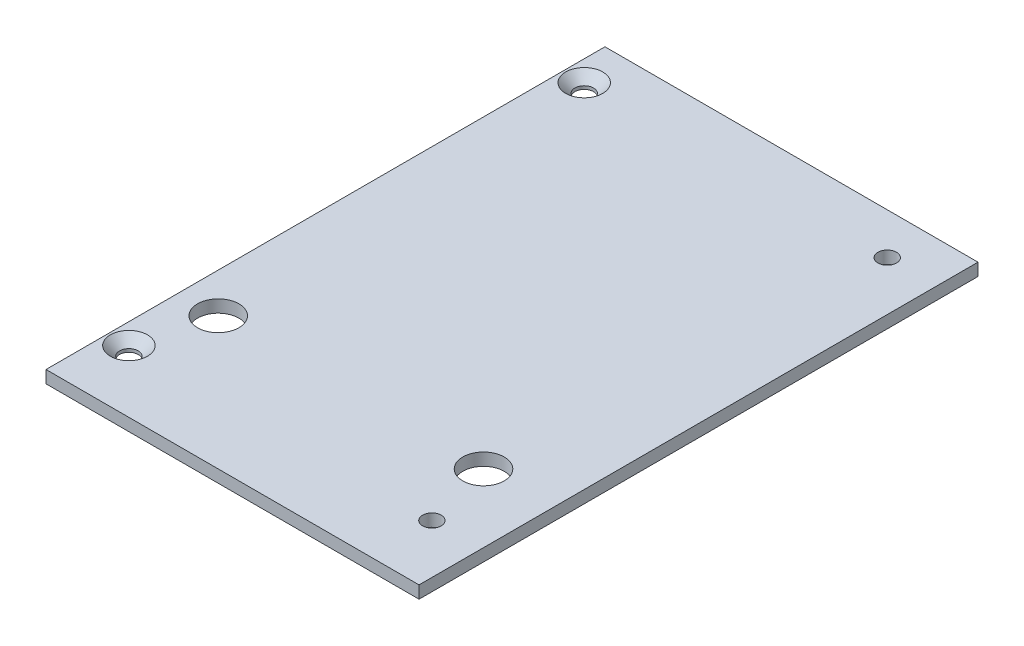
SolidWorks part; units mm, degrees
ref_plane "Alzado" through (0, 0, 0) normal (0, 0, 1) x (1, 0, 0)
ref_plane "Planta" through (0, 0, 0) normal (0, 1, 0) x (1, 0, 0)
ref_plane "Vista lateral" through (0, 0, 0) normal (1, 0, 0) x (0, 0, -1)
sketch "Sketch1" plane through (0, 0, 0) normal (0, 1, 0) x (1, 0, 0)
  line L1 (-45, -67.425) -> (45, -67.425)
  line L2 (-45, -67.425) -> (-45, 67.425)
  line L3 (-45, 67.425) -> (45, 67.425)
  line L4 (45, -67.425) -> (45, 67.425)
  line L5 (-45, -67.425) -> (45, 67.425) construction
  line L6 (-45, 67.425) -> (45, -67.425) construction
  circle A0 centre (-40, 57.425) radius 2.25
  circle A1 centre (33.1, 57.425) radius 2.25
  circle A2 centre (33.1, -52.425) radius 2.25
  circle A3 centre (-40, -52.425) radius 2.25
  point P0 (0, 0)
  dimension "D1" = 134.85
  dimension "D2" = 90
extrude "Boss-Extrude1" add sketch "Sketch1" along normal blind 3
sketch "Sketch2" plane through (0, 0, 0) normal (0, -1, 0) x (1, 0, 0)
  circle A0 centre (-35.45, 35.425) radius 5
  circle A1 centre (28.55, 35.425) radius 5
  dimension "D1" = 10
extrude "Cut-Extrude1" cut sketch "Sketch2" against normal blind 10
sketch "Sketch3" plane through (0, 0, 0) normal (0, -1, 0) x (1, 0, 0)
  line L0 (-35, -67.425) -> (28.1, -67.425) construction
  line L1 (45, -67.425) -> (-45, -67.425) construction
  line L2 (-35, -72.8739) -> (-35, -0.3806) construction
  line L3 (28.1, -0.3806) -> (28.1, -72.8739) construction
  line L4 (28.1, -67.425) -> (28.1, -0.3806) construction
  line L5 (27.3285, 2.2876) -> (0.7785, 44.3637) construction
  line L6 (-34.2285, 2.2876) -> (-7.6785, 44.3637) construction
  line L7 (-7.6785, 44.3637) -> (-34.2285, 2.2876) construction
  line L8 (-35, -0.3806) -> (-35, -67.425) construction
  line L9 (-34.6, -0.3806) -> (-34.6, -67.025)
  line L10 (-34.6, -67.025) -> (27.7, -67.025)
  line L11 (27.7, -67.025) -> (27.7, -0.3806)
  line L12 (26.9903, 2.0741) -> (0.4403, 44.1502)
  line L13 (-7.3403, 44.1502) -> (-33.8903, 2.0741)
  line L14 (-29.6, -0.4963) -> (-29.6, -62.025)
  line L15 (-29.6, -62.025) -> (22.7, -62.025)
  line L16 (22.7, -62.025) -> (22.7, -0.4963)
  line L17 (22.7, -0.4963) -> (-3.45, 40.9459)
  line L18 (-3.45, 40.9459) -> (-29.6, -0.4963)
  arc A0 (28.1, -0.3806) -> (27.3285, 2.2876) centre (23.1, -0.3806) ccw construction
  arc A1 (28.1, -0.3806) -> (27.3285, 2.2876) centre (23.1, -0.3806) ccw construction
  arc A2 (0.7785, 44.3637) -> (-7.6785, 44.3637) centre (-3.45, 41.6954) ccw construction
  arc A3 (-34.2285, 2.2876) -> (-35, -0.3806) centre (-30, -0.3806) ccw construction
  arc A4 (-34.2285, 2.2876) -> (-35, -0.3806) centre (-30, -0.3806) ccw construction
  arc A5 (27.7, -0.3806) -> (26.9903, 2.0741) centre (23.1, -0.3806) ccw
  arc A6 (0.4403, 44.1502) -> (-7.3403, 44.1502) centre (-3.45, 41.6954) ccw
  arc A7 (-33.8903, 2.0741) -> (-34.6, -0.3806) centre (-30, -0.3806) ccw
  arc A8 (22.7, -0.4963) -> (22.7, -0.4963) centre (22.7, -0.4963) ccw
  arc A9 (-3.45, 40.9459) -> (-3.45, 40.9459) centre (-3.45, 40.9459) ccw
  arc A10 (-29.6, -0.4963) -> (-29.6, -0.4963) centre (-29.6, -0.4963) ccw
  dimension "D1" = 0.4
  dimension "D2" = 5
extrude "Boss-Extrude2" add sketch "Sketch3" along normal blind 3
fillet "Fillet1" radius 10 5 edges at (9.625, 0, 20.2248) (22.7, 0, -31.2606) (-3.45, 0, -62.025) (-29.6, 0, -31.2606) (-16.525, 0, 20.2248)
sketch "Sketch4" plane through (0, 3, 0) normal (0, 1, 0) x (1, 0, 0)
  line L0 (-40, 57.425) -> (33.1, 57.425) construction
  line L1 (-40, -52.425) -> (33.1, -52.425) construction
  line L3 (-45, 67.425) -> (-45, -67.425) construction
  line L4 (28.1, 0.3806) -> (28.1, 72.8739) construction
  line L5 (-45, -67.425) -> (45, -67.425) construction
  line L6 (45, 67.425) -> (-45, 67.425) construction
  dimension "D1" = 5
  dimension "D2" = 5
  dimension "D3" = 15
  dimension "D4" = 10
hole_wizard "Avellanado para tornillo tapón avellanado de clavija hexagonal de M41" positions "Croquis3D1" profile "Croquis1" countersink size "M4" standard "ISO"
sketch3d "Croquis3D1"
  line L0 (-40, 3, 52.425) -> (-40, 0, 52.425) construction
  line L1 (-40, 3, -57.425) -> (-40, 0, -57.425) construction
  point P0 (-40, 3, 52.425)
  point P5 (-40, 3, -57.425)
sketch "Croquis1" plane through (-40, 3, 52.425) normal (1, 0, 0) x (0, 0, 1)
  line L0 (0, 0) -> (0, 7.3519)
  line L1 (0, 7.3519) -> (2.25, 6)
  line L2 (2.25, 6) -> (2.25, 2.23)
  line L3 (2.25, 2.23) -> (4.48, 0)
  line L5 (4.48, 0) -> (0, 0)
  line L6 (-2.25, 2.23) -> (-4.48, 0) construction
  line L10 (0, 7.3519) -> (-2.25, 6) construction
  line L11 (0, -6.35) -> (0, 107.95) construction
  dimension "Diámetro de taladro" = 4.5
  dimension "Profundidad de taladro" = 6
  dimension "Ángulo de avellanado cercano" = 8.96
  dimension "Ángulo de avellanado lejano" = 90
  dimension "Ángulo de perforador" = 118
